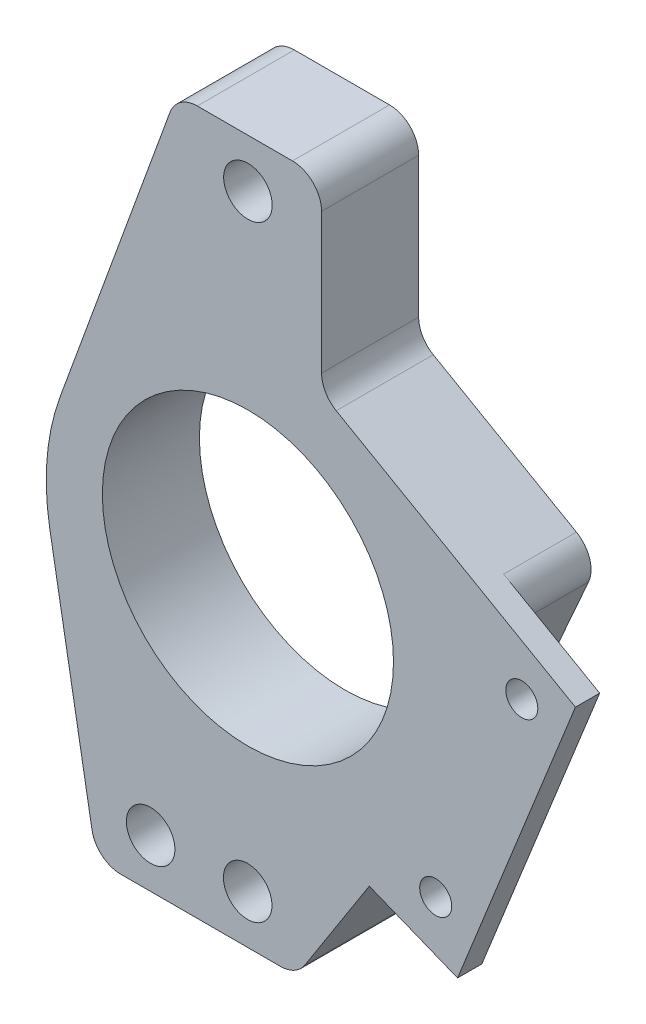
SolidWorks part; units mm, degrees
ref_plane "Front Plane" through (0, 0, 0) normal (0, 0, 1) x (1, 0, 0)
ref_plane "Top Plane" through (0, 0, 0) normal (0, 1, 0) x (1, 0, 0)
ref_plane "Right Plane" through (0, 0, 0) normal (1, 0, 0) x (0, 0, -1)
sketch "Sketch1" plane through (0, 0, 0) normal (0, 0, 1) x (1, 0, 0)
  line L0 (-18.5763, 100.3652) -> (19.2813, 100.3652)
  line L1 (19.2813, 100.3652) -> (19.2813, 51.6625)
  line L2 (19.2813, 51.6625) -> (85.7172, 13.5763)
  line L3 (85.7172, 13.5763) -> (54.8677, -63.2338)
  line L7 (12.6678, -83.786) -> (-39.7037, -83.786)
  line L9 (-39.7037, -83.786) -> (-51.867, -14.6914)
  line L13 (-49.1135, 16.6221) -> (-18.5763, 100.3652)
  line L14 (54.8677, -63.2338) -> (31.7649, -53.955)
  line L15 (31.7649, -53.955) -> (12.6678, -83.786)
  circle A0 centre (0, 0) radius 38.1
  circle A3 centre (0, 87.6652) radius 6.35
  circle A4 centre (-0.0617, -71.086) radius 6.35
  arc A5 (-49.1135, 16.6221) -> (-51.867, -14.6914) centre (7.9035, -4.1694) ccw
  circle A6 centre (-25.4617, -71.0752) radius 6.35
  dimension "D1" = 76.2
  dimension "D2" = 12.7
  dimension "D3" = 25.4
  dimension "D4" = 12.7
extrude "Boss-Extrude1" add sketch "Sketch1" along normal blind 25.4
sketch "Sketch2" plane through (0, 0, 0) normal (0, 0, 1) x (1, 0, 0)
  line L2 (85.7172, 13.5763) -> (54.8677, -63.2338)
  line L5 (85.7172, 13.5763) -> (66.5382, 24.5712)
  line L6 (85.7172, 13.5763) -> (19.2813, 51.6625) construction
  line L7 (66.5382, 24.5712) -> (31.7649, -53.955)
  line L8 (54.8677, -63.2338) -> (31.7649, -53.955)
extrude "Cut-Extrude1" cut sketch "Sketch2" along normal blind 19.05 contours L8 L7 L5 L2
sketch "Sketch3" plane through (0, 0, 25.4) normal (0, 0, 1) x (1, 0, 0)
  circle A0 centre (71.6792, 8.3618) radius 4.191
  circle A1 centre (49.1489, -47.7348) radius 4.191
  dimension "D1" = 8.382
  dimension "D2" = 8.382
  dimension "D3" = 60.452
extrude "Cut-Extrude2" cut sketch "Sketch3" against normal through all
fillet "Fillet1" radius 7.62 6 edges at (-18.5763, 100.3652, 12.7) (19.2813, 100.3652, 12.7) (19.2813, 51.6625, 12.7) (66.5382, 24.5712, 9.525) (12.6678, -83.786, 12.7) (-39.7037, -83.786, 12.7)
sketch "Sketch4" plane through (0, 0, 0) normal (0, 0, -1) x (-1, 0, 0)
  line L0 (-6.8055, 69.5132) -> (-6.8055, 54.6316)
  line L1 (-6.8055, 54.6316) -> (22.6967, 45.7548)
  line L2 (22.6967, 45.7548) -> (13.7587, 69.5132)
  line L3 (13.7587, 69.5132) -> (-6.8055, 69.5132)
  line L4 (31.8346, -36.2248) -> (13.7587, -45.3627)
  line L5 (13.7587, -45.3627) -> (18.2277, -54.2029)
  line L6 (18.2277, -54.2029) -> (29.5754, -54.2029)
  line L7 (29.5754, -54.2029) -> (31.8346, -36.2248)
  line L8 (-23.2536, -45.3627) -> (-17.1428, -57.4508)
  line L9 (-17.1428, -57.4508) -> (-3.4114, -57.4508)
  line L10 (-3.4114, -57.4508) -> (-10.2771, -43.8697)
  line L11 (-10.2771, -43.8697) -> (-23.2536, -45.3627)
